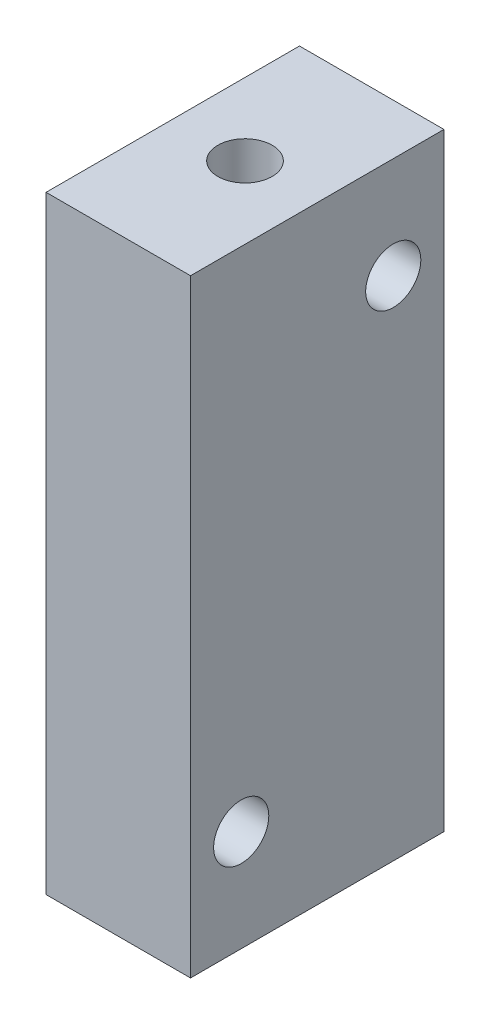
SolidWorks part; units mm, degrees
ref_plane "Front Plane" through (0, 0, 0) normal (1, 0, 0) x (0, 1, 0)
ref_plane "Top Plane" through (0, 0, 0) normal (0, 0, 1) x (0, 1, 0)
ref_plane "Right Plane" through (0, 0, 0) normal (0, 1, 0) x (-1, 0, 0)
sketch "Sketch1" plane through (0, 0, 0) normal (1, 0, 0) x (0, 1, 0)
  line L1 (19.05, -7.9375) -> (-19.05, -7.9375)
  line L2 (19.05, -7.9375) -> (19.05, 7.9375)
  line L3 (19.05, 7.9375) -> (-19.05, 7.9375)
  line L4 (-19.05, -7.9375) -> (-19.05, 7.9375)
  line L5 (19.05, -7.9375) -> (-19.05, 7.9375) construction
  line L6 (19.05, 7.9375) -> (-19.05, -7.9375) construction
  point P0 (0, 0)
  dimension "D1" = 15.875
  dimension "D2" = 38.1
extrude "Boss-Extrude1" add sketch "Sketch1" along normal blind 7.9375
sketch "Sketch3" plane through (0, -19.05, 0) normal (0, -1, 0) x (1, 0, 0)
  line L1 (9.05, -7.9375) -> (0, -7.9375)
  line L2 (9.05, -7.9375) -> (9.05, 7.9375)
  line L3 (9.05, 7.9375) -> (0, 7.9375)
  line L4 (0, -7.9375) -> (0, 7.9375)
  line L5 (9.05, -7.9375) -> (0, 7.9375) construction
  line L6 (9.05, 7.9375) -> (0, -7.9375) construction
  circle A0 centre (4.525, 0) radius 1.7
  circle A1 centre (4.525, 0) radius 5 construction
  point P2 (9.525, 0)
  point P3 (2.825, 0)
  point P6 (-19.05, 0)
  line M3 (7.9375, -7.9375) -> (7.9375, 7.9375)
  dimension "D1" = 3.4
  dimension "D2" = 10
  dimension "D3" = 28.575
  dimension "D4" = 19.05
extrude "Cut-Extrude1" cut sketch "Sketch3" against normal blind 49.4665 contours A0 region at (4.525, -19.05, 0)
extrude "Boss-Extrude2" add sketch "Sketch3<3>" against normal up to surface (38.1 mm away) contours L2 L3 L1 M3 region at (8.4937, -19.05, 0) up to face at (4.525, 19.05, -1.7)
sketch "Sketch3<3>" plane through (0, -19.05, 0) normal (0, -1, 0) x (1, 0, 0) same geometry as "Sketch3"
sketch "Sketch4" plane through (9.05, 0, 0) normal (1, 0, 0) x (0, 1, 0)
  line L0 (-19.05, -7.9375) -> (-19.05, 7.9375) construction
  line L1 (12.7, -4.7625) -> (-12.7, -4.7625) construction
  line L2 (12.7, -4.7625) -> (12.7, 4.7625) construction
  line L3 (12.7, 4.7625) -> (-12.7, 4.7625) construction
  line L4 (-12.7, -4.7625) -> (-12.7, 4.7625) construction
  line L5 (12.7, -4.7625) -> (-12.7, 4.7625) construction
  line L6 (12.7, 4.7625) -> (-12.7, -4.7625) construction
  line L9 (19.05, 7.9375) -> (-19.05, 7.9375) construction
  circle A0 centre (-12.7, 4.7625) radius 1.7272
  circle A2 centre (12.7, -4.7625) radius 1.7272
  point P0 (0, 0)
  dimension "D3" = 3.4544
  dimension "D1" = 3.175
  dimension "D2" = 6.35
extrude "Cut-Extrude2" cut sketch "Sketch4" against normal blind 22.2885 and the other way blind 3.302
